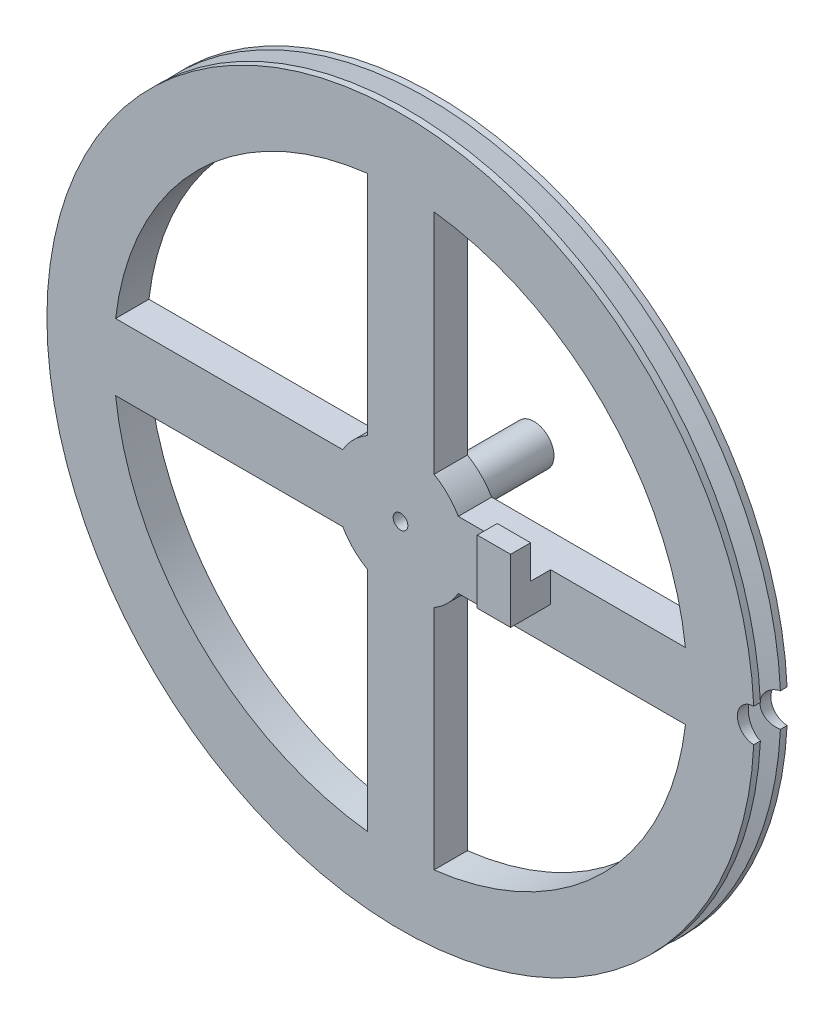
SolidWorks part; units mm, degrees
ref_plane "Front Plane" through (0, 0, 0) normal (0, 0, 1) x (1, 0, 0)
ref_plane "Top Plane" through (0, 0, 0) normal (0, 1, 0) x (1, 0, 0)
ref_plane "Right Plane" through (0, 0, 0) normal (1, 0, 0) x (0, 0, -1)
sketch "Sketch2" plane through (0, 0, 0) normal (0, 1, 0) x (1, 0, 0)
  line L0 (53, -1.5) -> (49, -0.5)
  line L2 (50, 2.5) -> (0, 2.5)
  line L4 (50, -2.5) -> (0, -2.5)
  line L5 (0, 2.5) -> (0, -2.5)
  line L6 (50, 2.5) -> (53, 2.5)
  line L11 (49, 0.5) -> (49, -0.5)
  line L13 (53, 2.5) -> (53, 1.5)
  line L16 (50, -2.5) -> (53, -2.5)
  line L17 (53, -1.5) -> (53, -2.5)
  line L18 (53, 1.5) -> (49, 0.5)
  point P3 (25, 0)
  dimension "D1" = 50
  dimension "D5" = 3
revolve "Revolve1" add sketch "Sketch2" angle 360 about L5
sketch "Sketch4" plane through (0, 0, 2.5) normal (0, 0, 1) x (1, 0, 0)
  line L18 (5.027, 8.6446) -> (5.027, 42.7051)
  line L20 (-4.973, -42.7115) -> (-4.973, -8.6758)
  line L22 (5.027, -42.7051) -> (5.027, -8.6446)
  line L24 (8.6603, 5) -> (42.7083, 5)
  line L25 (8.6603, -5) -> (42.7083, -5)
  line L26 (-42.7083, 5) -> (-8.6603, 5)
  line L29 (-42.7083, -5) -> (-8.6603, -5)
  line L31 (-4.973, 8.6758) -> (-4.973, 42.7115)
  arc A3 (-8.6603, -5) -> (-4.973, -8.6758) centre (0, 0) ccw
  arc A13 (-42.7083, -5) -> (-4.973, -42.7115) centre (0, 0) ccw
  arc A14 (-4.973, 8.6758) -> (-8.6603, 5) centre (0, 0) ccw
  arc A15 (-4.973, 42.7115) -> (-42.7083, 5) centre (0, 0) ccw
  arc A16 (8.6603, 5) -> (5.027, 8.6446) centre (0, 0) ccw
  arc A17 (42.7083, 5) -> (5.027, 42.7051) centre (0, 0) ccw
  arc A18 (5.027, -42.7051) -> (42.7083, -5) centre (0, 0) ccw
  arc A19 (5.027, -8.6446) -> (8.6603, -5) centre (0, 0) ccw
  dimension "D2" = 20
extrude "Cut-Extrude2" cut sketch "Sketch4" against normal up to next
sketch "Sketch6" plane through (0, 0, 2.5) normal (0, 0, 1) x (1, 0, 0)
  line L0 (17.5, 0.5) -> (17.5, 5)
  line L1 (8.6603, 5) -> (42.7083, 5) construction
  line L2 (17.5, 5) -> (22.5, 5)
  line L3 (22.5, 5) -> (22.5, 0.5)
  line L4 (17.5, 0.5) -> (22.5, 0.5)
  dimension "D2" = 4.5
  dimension "D1" = 5
  dimension "D3" = 17.5
  dimension "D4" = 4.5
extrude "Boss-Extrude1" add sketch "Sketch6" along normal blind 6
sketch "Sketch7" plane through (0, 5, 0) normal (0, 1, 0) x (1, 0, 0)
  line L0 (22.5, -8.5) -> (22.5, -2.5) construction
  line L1 (17.5, -8.5) -> (22.5, -8.5)
  line L2 (17.5, -8.5) -> (17.5, -5.5)
  line L3 (17.5, -5.5) -> (22.5, -5.5)
  line L4 (22.5, -8.5) -> (22.5, -5.5)
  dimension "D1" = 3
extrude "Boss-Extrude2" add sketch "Sketch7" along normal blind 5
sketch "Sketch9" plane through (0, 0, 2.5) normal (0, 0, 1) x (1, 0, 0)
  line L0 (0, 0) -> (69.7598, 0)
sketch "Sketch23" plane through (0, 0, -2.5) normal (0, 0, -1) x (-1, 0, 0)
  circle A0 centre (0, 0) radius 3
  dimension "D1" = 6
extrude "Boss-Extrude5" add sketch "Sketch23" along normal blind 15
ref_plane "Plane2" through (0, 0, 0) normal (0, -1, 0) x (1, 0, 0)
sketch "Sketch18" plane through (0, 0, 2.5) normal (0, 0, 1) x (1, 0, 0)
  line L0 (-58.3, 0) -> (58.3, 0) construction
  circle A0 centre (51.75, 0) radius 1.25
  dimension "D1" = 2.5
extrude "Boss-Extrude3" [suppressed] add sketch "Sketch18" against normal blind 5
sketch "Sketch19" plane through (0, 0, 2.5) normal (0, 0, 1) x (1, 0, 0)
  circle A0 centre (0, 0) radius 3
  dimension "D1" = 6
extrude "Boss-Extrude4" [suppressed] add sketch "Sketch19" along normal blind 2
sketch "Sketch5" plane through (0, 0, 2.5) normal (0, 0, 1) x (1, 0, 0)
  circle A0 centre (0, 0) radius 1.1
  dimension "D1" = 2.2
extrude "Cut-Extrude3" cut sketch "Sketch5" against normal through all and the other way through all
sketch "Sketch20" plane through (0, 0, 0) normal (0, -1, 0) x (1, 0, 0)
  arc A0 (52.3139, -2) -> (52.3139, 2) centre (52.3139, 0) ccw
  dimension "D1" = 4
sweep "Sweep1" [suppressed] add path "Sketch20" circular profile diameter 1 parameters "D3"=1
ref_plane "Plane3" through (49, 0, 0) normal (1, 0, 0) x (0, 0, -1)
sketch "Sketch21" plane through (49, 0, 0) normal (1, 0, 0) x (0, 0, -1)
  circle A0 centre (0, 0) radius 0.25
  dimension "D1" = 0.5
sketch "Sketch22" plane through (0, 0, 0) normal (0, 0, 1) x (1, 0, 0)
  circle A0 centre (53, 0) radius 2.5
  dimension "D1" = 5
extrude "Cut-Extrude4" cut sketch "Sketch22" against normal through all and the other way through all
extrude "Cut-Extrude5" cut sketch "Sketch21" against normal blind 2.5
